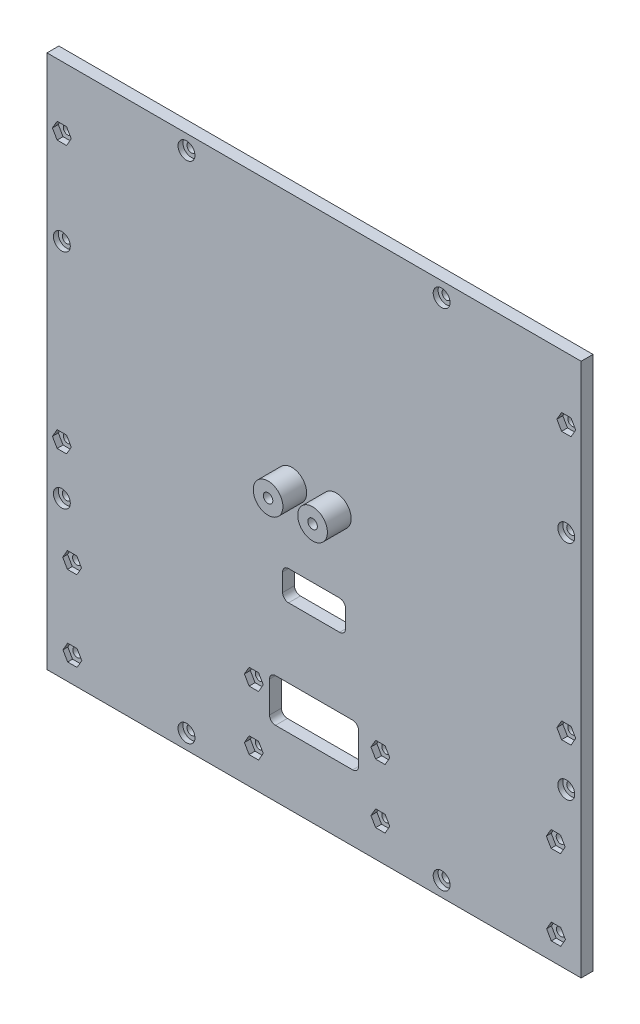
SolidWorks part; units mm, degrees
ref_plane "Alzado" through (0, 0, 0) normal (0, 0, 1) x (1, 0, 0)
ref_plane "Planta" through (0, 0, 0) normal (0, 1, 0) x (1, 0, 0)
ref_plane "Vista lateral" through (0, 0, 0) normal (1, 0, 0) x (0, 0, -1)
sketch "Croquis1" plane through (0, 0, 0) normal (0, 0, 1) x (1, 0, 0)
  line L1 (86, 72.7734) -> (-94, 72.7734)
  line L2 (86, 72.7734) -> (86, 252.7734)
  line L3 (86, 252.7734) -> (-94, 252.7734)
  line L4 (-94, 72.7734) -> (-94, 252.7734)
  line L5 (86, 72.7734) -> (-94, 252.7734) construction
  line L6 (86, 252.7734) -> (-94, 72.7734) construction
  point P4 (-4, 162.7734)
extrude "Saliente-Extruir1" add sketch "Croquis1" along normal blind 4
sketch "Croquis14" plane through (0, 0, 4) normal (0, 0, 1) x (1, 0, 0)
  circle A0 centre (-89, 200.2734) radius 1.5 construction
  circle A1 centre (-89, 125.2734) radius 1.5 construction
  circle A2 centre (-46.9915, 247.7734) radius 1.5 construction
  circle A3 centre (38.9915, 247.7734) radius 1.5 construction
  circle A4 centre (81, 200.2734) radius 1.5 construction
  circle A5 centre (81, 125.2734) radius 1.5 construction
  circle A6 centre (-46.9915, 77.7734) radius 1.5 construction
  circle A7 centre (38.9915, 77.7734) radius 1.5 construction
  circle A8 centre (-89, 200.2734) radius 1.5
  circle A9 centre (-89, 125.2734) radius 1.5
  circle A10 centre (-46.9915, 247.7734) radius 1.5
  circle A11 centre (38.9915, 247.7734) radius 1.5
  circle A12 centre (81, 200.2734) radius 1.5
  circle A13 centre (81, 125.2734) radius 1.5
  circle A14 centre (-46.9915, 77.7734) radius 1.5
  circle A15 centre (38.9915, 77.7734) radius 1.5
extrude "Cortar-Extruir7" cut sketch "Croquis14" against normal up to next
sketch "Croquis15" plane through (0, 0, 4) normal (0, 0, 1) x (1, 0, 0)
  circle A0 centre (-46.9915, 77.7734) radius 2.85
  circle A1 centre (-89, 125.2734) radius 2.85
  circle A2 centre (-89, 200.2734) radius 2.85
  circle A3 centre (-46.9915, 247.7734) radius 2.85
  circle A4 centre (38.9915, 247.7734) radius 2.85
  circle A5 centre (81, 200.2734) radius 2.85
  circle A6 centre (81, 125.2734) radius 2.85
  circle A7 centre (38.9915, 77.7734) radius 2.85
  dimension "D1" = 5.7
extrude "Cortar-Extruir8" cut sketch "Croquis15" against normal blind 1.65
sketch "Croquis16" plane through (0, 0, 4) normal (0, 0, 1) x (1, 0, 0)
  line L1 (19.9277, 82.0234) -> (21.5154, 84.7734)
  line L2 (21.5154, 84.7734) -> (19.9277, 87.5234)
  line L3 (19.9277, 87.5234) -> (16.7523, 87.5234)
  line L4 (16.7523, 87.5234) -> (15.1646, 84.7734)
  line L5 (15.1646, 84.7734) -> (16.7523, 82.0234)
  line L6 (16.7523, 82.0234) -> (19.9277, 82.0234)
  line L7 (-22.7123, 82.0234) -> (-21.1246, 84.7734)
  line L8 (-21.1246, 84.7734) -> (-22.7123, 87.5234)
  line L9 (-22.7123, 87.5234) -> (-25.8877, 87.5234)
  line L10 (-25.8877, 87.5234) -> (-27.4754, 84.7734)
  line L11 (-27.4754, 84.7734) -> (-25.8877, 82.0234)
  line L12 (-25.8877, 82.0234) -> (-22.7123, 82.0234)
  line L13 (-22.7123, 102.0256) -> (-21.1246, 104.7756)
  line L14 (-21.1246, 104.7756) -> (-22.7123, 107.5256)
  line L15 (-22.7123, 107.5256) -> (-25.8877, 107.5256)
  line L16 (-25.8877, 107.5256) -> (-27.4754, 104.7756)
  line L17 (-27.4754, 104.7756) -> (-25.8877, 102.0256)
  line L18 (-25.8877, 102.0256) -> (-22.7123, 102.0256)
  line L19 (19.9277, 102.0256) -> (21.5154, 104.7756)
  line L20 (21.5154, 104.7756) -> (19.9277, 107.5256)
  line L21 (19.9277, 107.5256) -> (16.7523, 107.5256)
  line L22 (16.7523, 107.5256) -> (15.1646, 104.7756)
  line L23 (15.1646, 104.7756) -> (16.7523, 102.0256)
  line L24 (16.7523, 102.0256) -> (19.9277, 102.0256)
  circle A0 centre (18.34, 104.7756) radius 1.5
  circle A1 centre (-24.3, 104.7756) radius 1.5
  circle A2 centre (18.34, 84.7734) radius 1.5
  circle A3 centre (-24.3, 84.7734) radius 1.5
  circle A4 centre (18.34, 84.7734) radius 2.75 construction
  circle A5 centre (-24.3, 84.7734) radius 2.75 construction
  circle A6 centre (-24.3, 104.7756) radius 2.75 construction
  circle A7 centre (18.34, 104.7756) radius 2.75 construction
  dimension "D1" = 5.5
  dimension "D5" = 3
  dimension "D2" = 5.5
  dimension "D3" = 5.5
  dimension "D4" = 5.5
extrude "Cortar-Extruir9" cut sketch "Croquis16" against normal blind 2
sketch "Croquis17" plane through (0, 0, 4) normal (0, 0, 1) x (1, 0, 0)
  circle A0 centre (18.34, 104.7756) radius 1.5 construction
  circle A1 centre (18.34, 104.7756) radius 1.5
  circle A2 centre (18.34, 84.7734) radius 1.5 construction
  circle A3 centre (18.34, 84.7734) radius 1.5
  circle A4 centre (-24.3, 84.7734) radius 1.5 construction
  circle A5 centre (-24.3, 84.7734) radius 1.5
  circle A6 centre (-24.3, 104.7756) radius 1.5 construction
  circle A7 centre (-24.3, 104.7756) radius 1.5
extrude "Cortar-Extruir10" cut sketch "Croquis17" against normal up to next
sketch "Croquis18" plane through (0, 0, 4) normal (0, 0, 1) x (1, 0, 0)
  line L0 (-4, 252.7734) -> (-4, 72.7734) construction
  line L13 (-22.7123, 107.5256) -> (-25.8877, 107.5256) construction
  line L14 (9, 95.0256) -> (-17, 95.0256)
  line L15 (86, 252.7734) -> (-94, 252.7734) construction
  line L16 (-94, 72.7734) -> (86, 72.7734) construction
  line L17 (11, 97.0256) -> (11, 107.5256)
  line L18 (9, 109.5256) -> (-17, 109.5256)
  line L19 (-19, 97.0256) -> (-19, 107.5256)
  line L20 (11, 95.0256) -> (-19, 109.5256) construction
  line L21 (11, 109.5256) -> (-19, 95.0256) construction
  line L22 (-25.8877, 102.0256) -> (-22.7123, 102.0256) construction
  arc A0 (11, 107.5256) -> (9, 109.5256) centre (9, 107.5256) ccw
  arc A1 (9, 95.0256) -> (11, 97.0256) centre (9, 97.0256) ccw
  arc A2 (-17, 95.0256) -> (-19, 97.0256) centre (-17, 97.0256) cw
  arc A3 (-17, 109.5256) -> (-19, 107.5256) centre (-17, 107.5256) ccw
  point P0 (-4, 102.2756)
  point P11 (-24.3, 102.0256)
  dimension "D1" = 2
  dimension "D4" = 2
  dimension "D2" = 7
  dimension "D3" = 30
sketch "Croquis19" plane through (0, 0, 4) normal (0, 0, 1) x (1, 0, 0)
  circle A0 centre (-85.5357, 108.2256) radius 1.5 construction
  circle A1 centre (-85.45, 81.2376) radius 1.5 construction
  circle A2 centre (77.45, 108.3114) radius 1.5 construction
  circle A3 centre (77.5357, 81.3234) radius 1.5 construction
  circle A4 centre (-85.5357, 108.2256) radius 1.5
  circle A5 centre (-85.45, 81.2376) radius 1.5
  circle A6 centre (77.45, 108.3114) radius 1.5
  circle A7 centre (77.5357, 81.3234) radius 1.5
extrude "Cortar-Extruir12" cut sketch "Croquis19" against normal up to next
sketch "Croquis20" plane through (0, 0, 4) normal (0, 0, 1) x (1, 0, 0)
  line L1 (-83.8623, 78.4876) -> (-82.2746, 81.2376)
  line L2 (-82.2746, 81.2376) -> (-83.8623, 83.9876)
  line L3 (-83.8623, 83.9876) -> (-87.0377, 83.9876)
  line L4 (-87.0377, 83.9876) -> (-88.6254, 81.2376)
  line L5 (-88.6254, 81.2376) -> (-87.0377, 78.4876)
  line L6 (-87.0377, 78.4876) -> (-83.8623, 78.4876)
  line L7 (-87.1235, 105.4756) -> (-83.948, 105.4756)
  line L8 (-83.948, 105.4756) -> (-82.3603, 108.2256)
  line L9 (-82.3603, 108.2256) -> (-83.948, 110.9756)
  line L10 (-83.948, 110.9756) -> (-87.1235, 110.9756)
  line L11 (-87.1235, 110.9756) -> (-88.7112, 108.2256)
  line L12 (-88.7112, 108.2256) -> (-87.1235, 105.4756)
  line L13 (79.1235, 78.5734) -> (80.7112, 81.3234)
  line L14 (80.7112, 81.3234) -> (79.1235, 84.0734)
  line L15 (79.1235, 84.0734) -> (75.948, 84.0734)
  line L16 (75.948, 84.0734) -> (74.3603, 81.3234)
  line L17 (74.3603, 81.3234) -> (75.948, 78.5734)
  line L18 (75.948, 78.5734) -> (79.1235, 78.5734)
  line L19 (79.0377, 105.5614) -> (80.6254, 108.3114)
  line L20 (80.6254, 108.3114) -> (79.0377, 111.0614)
  line L21 (79.0377, 111.0614) -> (75.8623, 111.0614)
  line L22 (75.8623, 111.0614) -> (74.2746, 108.3114)
  line L23 (74.2746, 108.3114) -> (75.8623, 105.5614)
  line L24 (75.8623, 105.5614) -> (79.0377, 105.5614)
  circle A0 centre (-85.45, 81.2376) radius 2.75 construction
  circle A1 centre (-85.5357, 108.2256) radius 2.75 construction
  circle A2 centre (77.5357, 81.3234) radius 2.75 construction
  circle A3 centre (77.45, 108.3114) radius 2.75 construction
  dimension "D1" = 5.5
  dimension "D2" = 5.5
  dimension "D3" = 5.5
  dimension "D4" = 5.5
extrude "Cortar-Extruir13" cut sketch "Croquis20" against normal blind 1.65
sketch "Croquis21" plane through (0, 0, 4) normal (0, 0, 1) x (1, 0, 0)
  circle A0 centre (81, 231.7756) radius 1.5
  circle A1 centre (-89, 231.7756) radius 1.5
  circle A2 centre (81, 141.7756) radius 1.5
  circle A3 centre (-89, 141.7756) radius 1.5
  dimension "D1" = 3
  dimension "D2" = 3
  dimension "D3" = 3
  dimension "D4" = 3
extrude "Cortar-Extruir14" cut sketch "Croquis21" against normal up to next
sketch "Croquis22" plane through (0, 0, 4) normal (0, 0, 1) x (1, 0, 0)
  line L1 (82.5877, 139.0256) -> (84.1754, 141.7756)
  line L2 (84.1754, 141.7756) -> (82.5877, 144.5256)
  line L3 (82.5877, 144.5256) -> (79.4123, 144.5256)
  line L4 (79.4123, 144.5256) -> (77.8246, 141.7756)
  line L5 (77.8246, 141.7756) -> (79.4123, 139.0256)
  line L6 (79.4123, 139.0256) -> (82.5877, 139.0256)
  line L7 (-87.4123, 139.0256) -> (-85.8246, 141.7756)
  line L8 (-85.8246, 141.7756) -> (-87.4123, 144.5256)
  line L9 (-87.4123, 144.5256) -> (-90.5877, 144.5256)
  line L10 (-90.5877, 144.5256) -> (-92.1754, 141.7756)
  line L11 (-92.1754, 141.7756) -> (-90.5877, 139.0256)
  line L12 (-90.5877, 139.0256) -> (-87.4123, 139.0256)
  line L13 (-87.4123, 229.0256) -> (-85.8246, 231.7756)
  line L14 (-85.8246, 231.7756) -> (-87.4123, 234.5256)
  line L15 (-87.4123, 234.5256) -> (-90.5877, 234.5256)
  line L16 (-90.5877, 234.5256) -> (-92.1754, 231.7756)
  line L17 (-92.1754, 231.7756) -> (-90.5877, 229.0256)
  line L18 (-90.5877, 229.0256) -> (-87.4123, 229.0256)
  line L19 (82.5877, 229.0256) -> (84.1754, 231.7756)
  line L20 (84.1754, 231.7756) -> (82.5877, 234.5256)
  line L21 (82.5877, 234.5256) -> (79.4123, 234.5256)
  line L22 (79.4123, 234.5256) -> (77.8246, 231.7756)
  line L23 (77.8246, 231.7756) -> (79.4123, 229.0256)
  line L24 (79.4123, 229.0256) -> (82.5877, 229.0256)
  circle A0 centre (81, 141.7756) radius 2.75 construction
  circle A1 centre (-89, 141.7756) radius 2.75 construction
  circle A2 centre (-89, 231.7756) radius 2.75 construction
  circle A3 centre (81, 231.7756) radius 2.75 construction
  dimension "D1" = 5.5
  dimension "D2" = 5.5
  dimension "D3" = 5.5
  dimension "D4" = 5.5
extrude "Cortar-Extruir15" cut sketch "Croquis22" against normal blind 2
sketch "Croquis23" plane through (0, 0, 4) normal (0, 0, 1) x (1, 0, 0)
  line L0 (-4, 252.7734) -> (-4, 72.7734) construction
  line L1 (86, 252.7734) -> (-94, 252.7734) construction
  line L2 (-94, 72.7734) -> (86, 72.7734) construction
  line L3 (-94, 162.7734) -> (86, 162.7734) construction
  line L4 (-94, 252.7734) -> (-94, 72.7734) construction
  line L5 (86, 72.7734) -> (86, 252.7734) construction
  line L7 (6, 154.9734) -> (-14, 154.9734)
  line L8 (6, 154.9734) -> (6, 170.5734)
  line L9 (6, 170.5734) -> (-14, 170.5734)
  line L10 (-14, 154.9734) -> (-14, 170.5734)
  line L11 (6, 154.9734) -> (-14, 170.5734) construction
  line L12 (6, 170.5734) -> (-14, 154.9734) construction
  line L13 (-11.5, 171.5375) -> (-14.5, 169.8054)
  line L14 (-14.5, 169.8054) -> (-14.5, 166.3413)
  line L15 (-14.5, 166.3413) -> (-11.5, 164.6093)
  line L16 (-11.5, 164.6093) -> (-8.5, 166.3413)
  line L17 (-8.5, 166.3413) -> (-8.5, 169.8054)
  line L18 (-8.5, 169.8054) -> (-11.5, 171.5375)
  line L19 (3.5, 171.5375) -> (0.5, 169.8054)
  line L20 (0.5, 169.8054) -> (0.5, 166.3413)
  line L21 (0.5, 166.3413) -> (3.5, 164.6093)
  line L22 (3.5, 164.6093) -> (6.5, 166.3413)
  line L23 (6.5, 166.3413) -> (6.5, 169.8054)
  line L24 (6.5, 169.8054) -> (3.5, 171.5375)
  line L25 (6.6, 132.9734) -> (-14.6, 132.9734)
  line L26 (6.6, 132.9734) -> (6.6, 142.9734)
  line L27 (6.6, 142.9734) -> (-14.6, 142.9734)
  line L28 (-14.6, 132.9734) -> (-14.6, 142.9734)
  line L29 (6.6, 132.9734) -> (-14.6, 142.9734) construction
  line L30 (6.6, 142.9734) -> (-14.6, 132.9734) construction
  circle A0 centre (-11.5, 168.0734) radius 1.6
  circle A1 centre (3.5, 168.0734) radius 1.6
  circle A2 centre (-11.5, 168.0734) radius 5
  circle A3 centre (3.5, 168.0734) radius 5
  circle A6 centre (-11.5, 168.0734) radius 3 construction
  circle A7 centre (3.5, 168.0734) radius 3 construction
  point P12 (-4, 162.7734)
  point P23 (-4, 137.9734)
  dimension "D3" = 6
  dimension "D6" = 3.2
  dimension "D7" = 3.2
  dimension "D9" = 10
  dimension "D10" = 10
  dimension "D11" = 10
  dimension "D4" = 6
  dimension "D1" = 20
  dimension "D2" = 15.6
  dimension "D5" = 21.2
  dimension "D8" = 2.5
  dimension "D12" = 12
  dimension "D13" = 15
  dimension "D14" = 2.5
  dimension "D15" = 2.5
extrude "Saliente-Extruir2" add sketch "Croquis23" along normal blind 8 contours A2 | A0 | A3 | A1
extrude "Cortar-Extruir16" cut sketch "Croquis23<4>" along normal blind 2.7 from offset 2 contours L16 L17 L18 L13 L14 L15 | L21 L22 L23 L24 L19 L20
sketch "Croquis23<4>" plane through (0, 0, 4) normal (0, 0, 1) x (1, 0, 0) same geometry as "Croquis23"
extrude "Cortar-Extruir17" cut sketch "Croquis23<5>" against normal blind 5 contours L28 L25 L26 L27 region at (-4, 137.9734, 4)
sketch "Croquis23<5>" plane through (0, 0, 4) normal (0, 0, 1) x (1, 0, 0) same geometry as "Croquis23"
fillet "Redondeo1" radius 2 4 edges at (-14.6, 132.9734, 2) (6.6, 132.9734, 2) (6.6, 142.9734, 2) (-14.6, 142.9734, 2)
extrude "Cortar-Extruir18" cut sketch "Croquis18" against normal up to next
